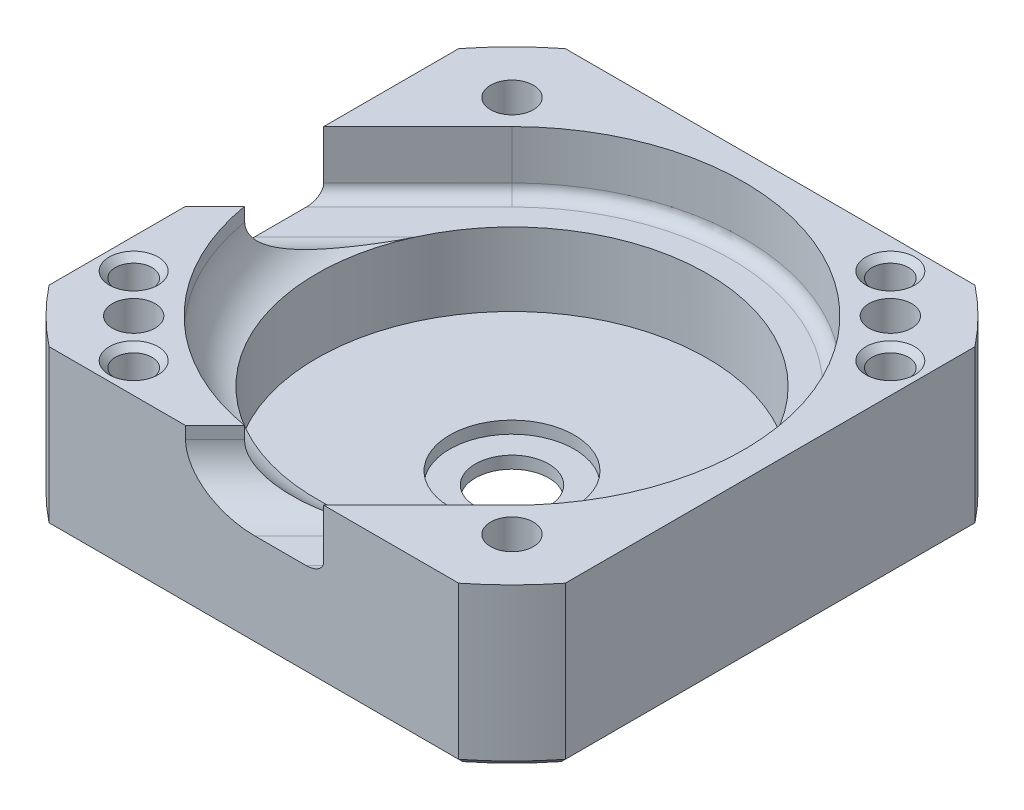
SolidWorks part; units mm, degrees
ref_plane "Front Plane" through (0, 0, 0) normal (0, 0, 1) x (1, 0, 0)
ref_plane "Top Plane" through (0, 0, 0) normal (0, 1, 0) x (1, 0, 0)
ref_plane "Right Plane" through (0, 0, 0) normal (1, 0, 0) x (0, 0, -1)
sketch "Sketch2" plane through (0, 0, 0) normal (0, 1, 0) x (1, 0, 0)
  line L1 (-21.15, 21.15) -> (21.15, 21.15)
  line L2 (-21.15, 21.15) -> (-21.15, -21.15)
  line L3 (-21.15, -21.15) -> (21.15, -21.15)
  line L4 (21.15, 21.15) -> (21.15, -21.15)
  line L5 (-21.15, 21.15) -> (21.15, -21.15) construction
  line L6 (-21.15, -21.15) -> (21.15, 21.15) construction
  point P0 (0, 0)
  dimension "D1" = 42.3
extrude "Boss-Extrude1" add sketch "Sketch2" along normal blind 13
sketch "Sketch3" plane through (0, 13, 0) normal (0, 1, 0) x (1, 0, 0)
  circle A0 centre (0, 0) radius 3
  dimension "D1" = 6
extrude "Cut-Extrude1" cut sketch "Sketch3" against normal through all
sketch "Sketch4" plane through (0, 13, 0) normal (0, 1, 0) x (1, 0, 0)
  line L1 (-15.5, 15.5) -> (15.5, 15.5) construction
  line L2 (-15.5, 15.5) -> (-15.5, -15.5) construction
  line L3 (-15.5, -15.5) -> (15.5, -15.5) construction
  line L4 (15.5, 15.5) -> (15.5, -15.5) construction
  line L5 (-15.5, 15.5) -> (15.5, -15.5) construction
  line L6 (-15.5, -15.5) -> (15.5, 15.5) construction
  circle A0 centre (-15.5, 15.5) radius 1.75
  circle A1 centre (15.5, 15.5) radius 1.75
  circle A2 centre (15.5, -15.5) radius 1.75
  circle A3 centre (-15.5, -15.5) radius 1.75
  point P0 (0, 0)
  point P16 (0, 0)
  dimension "D3" = 3.5
  dimension "D1" = 31
  dimension "D2" = 31
  dimension "D4" = 4
extrude "Cut-Extrude2" cut sketch "Sketch4" against normal through all
sketch "Sketch5" plane through (0, 13, 0) normal (0, 1, 0) x (1, 0, 0)
  circle A0 centre (0, 0) radius 27
  circle A1 centre (0, 0) radius 29.9106
  dimension "D1" = 54
extrude "Cut-Extrude4" cut sketch "Sketch5" against normal through all
sketch "Sketch6" plane through (0, 13, 0) normal (0, 1, 0) x (1, 0, 0)
  line L0 (-21.15, 5.7201) -> (-13.435, 13.435)
  line L1 (13.435, -13.435) -> (5.7201, -21.15)
  line L9 (-21.15, 16.7833) -> (-21.15, -16.7833) construction
  line L10 (-16.7833, -21.15) -> (16.7833, -21.15) construction
  line L11 (-7.7782, 7.7782) -> (-21.15, -5.5937) construction
  line L12 (5.7201, 21.15) -> (21.15, 5.7201) construction
  line L13 (7.3751, 21.15) -> (21.15, 7.3751) construction
  line L14 (16.7833, 21.15) -> (-16.7833, 21.15) construction
  line L15 (21.15, -16.7833) -> (21.15, 16.7833) construction
  line L18 (7.7782, -7.7782) -> (-5.5937, -21.15) construction
  line L19 (-21.15, 5.7201) -> (-21.15, -5.5937)
  line L21 (-3.1763, -18.7326) -> (-5.5937, -21.15)
  line L22 (-5.5937, -21.15) -> (5.7201, -21.15)
  line L23 (-18.7326, -3.1763) -> (-21.15, -5.5937)
  arc A0 (-13.435, 13.435) -> (13.435, -13.435) centre (0, 0) cw
  arc A2 (-18.7326, -3.1763) -> (-3.1763, -18.7326) centre (0, 0) ccw
  circle A3 centre (0, 0) radius 11 construction
  circle A5 centre (15.5, 15.5) radius 1.75 construction
  arc A6 (13.435, -13.435) -> (-13.435, 13.435) centre (0, 0) ccw
  circle M13 centre (0, 0) radius 3
  line M14 (-16.7833, -21.15) -> (16.7833, -21.15)
  line M20 (-21.15, 16.7833) -> (-21.15, -16.7833)
  dimension "D1" = 45
  dimension "D3" = 19
  dimension "D5" = 22
  dimension "D2" = 45
  dimension "D4" = 45
extrude "Cut-Extrude5" cut sketch "Sketch6" against normal offset from surface (11 mm away) 2 contours L23 A2 L21 L1 A0 L0 M14 M20 M13 region at (-16.891, 13, -9.176) up to face at (-15.5, 0, 17.25)
chamfer "Chamfer1" distance 1.8 angle 45 4 edges at (15.5, 0, -13.75) (-15.5, 0, -13.75) (-15.5, 0, 17.25) (15.5, 0, 17.25)
sketch "Sketch7" plane through (0, 2, 0) normal (0, 1, 0) x (1, 0, 0)
  circle A0 centre (0, 0) radius 5.1
  dimension "D1" = 10.2
extrude "Cut-Extrude6" cut sketch "Sketch7" against normal blind 1
sketch "Sketch8" plane through (0, 2, 0) normal (0, 1, 0) x (1, 0, 0)
  line L6 (-21.15, 5.7201) -> (-21.15, -5.5937)
  line L7 (-21.15, -5.5937) -> (-18.7326, -3.1763)
  line L8 (-3.1763, -18.7326) -> (-5.5937, -21.15)
  line L9 (-5.5937, -21.15) -> (5.7201, -21.15)
  line L10 (5.7201, -21.15) -> (13.435, -13.435)
  line L11 (-13.435, 13.435) -> (-21.15, 5.7201)
  line L12 (-21.15, 5.7201) -> (-21.15, -5.5937)
  line L13 (-21.15, -5.5937) -> (-18.7326, -3.1763)
  line L14 (-3.1763, -18.7326) -> (-5.5937, -21.15)
  line L15 (-5.5937, -21.15) -> (5.7201, -21.15)
  line L16 (5.7201, -21.15) -> (13.435, -13.435)
  line L17 (-13.435, 13.435) -> (-21.15, 5.7201)
  circle A0 centre (0, 0) radius 16
  arc A3 (-18.7326, -3.1763) -> (-3.1763, -18.7326) centre (0, 0) ccw
  arc A4 (13.435, -13.435) -> (-13.435, 13.435) centre (0, 0) ccw
  arc A5 (-18.7326, -3.1763) -> (-3.1763, -18.7326) centre (0, 0) ccw
  arc A6 (13.435, -13.435) -> (-13.435, 13.435) centre (0, 0) ccw
  dimension "D1" = 32
  dimension "D2" = 0
extrude "Boss-Extrude2" add sketch "Sketch8" along normal offset from surface (6 mm away) 5 up to face at (-15.5, 13, -13.75)
sketch "Sketch9" plane through (0, 13, 0) normal (0, 1, 0) x (1, 0, 0)
  line L0 (12.318, 18.682) -> (18.682, 12.318) construction
  line L1 (5.7201, -21.15) -> (16.7833, -21.15) construction
  line L2 (-19.0919, 19.0919) -> (19.0919, -19.0919) construction
  line L3 (-18.682, -12.318) -> (-12.318, -18.682) construction
  circle A0 centre (15.5, 15.5) radius 1.75 construction
  circle A1 centre (12.318, 18.682) radius 1.5
  circle A2 centre (18.682, 12.318) radius 1.5
  arc A3 (-16.7833, 21.15) -> (-21.15, 16.7833) centre (0, 0) ccw construction
  arc A4 (16.7833, -21.15) -> (21.15, -16.7833) centre (0, 0) ccw construction
  circle A5 centre (-12.318, -18.682) radius 1.5
  circle A6 centre (-18.682, -12.318) radius 1.5
  point P2 (15.5, 15.5)
  dimension "D2" = 3
  dimension "D3" = 3
  dimension "D1" = 4.5
  dimension "D4" = 45
extrude "Cut-Extrude7" cut sketch "Sketch9" against normal blind 3
chamfer "Chamfer3" distance 0.5 angle 45 4 edges at (12.318, 13, -17.182) (18.682, 13, -10.818) (-12.318, 13, 17.182) (-18.682, 13, 10.818)
fillet "Fillet4" radius 4 2 edges at (-4.385, 8, 19.9413) (-19.9413, 8, 4.385)
fillet "Fillet5" radius 4 1 edges at (-13.435, 8, 13.435)
chamfer "Chamfer4" distance 0.5 angle 45 8 edges at (19.0919, 0, 19.0919) (0, 0, 21.15) (-19.0919, 0, 19.0919) (-21.15, 0, 0) (-19.0919, 0, -19.0919) (0, 0, -21.15) (19.0919, 0, -19.0919) (21.15, 0, 0)
fillet "Fillet6" radius 1 3 edges at (9.5775, 8, 17.2925) (-17.2925, 8, -9.5775) (13.435, 8, -13.435)
